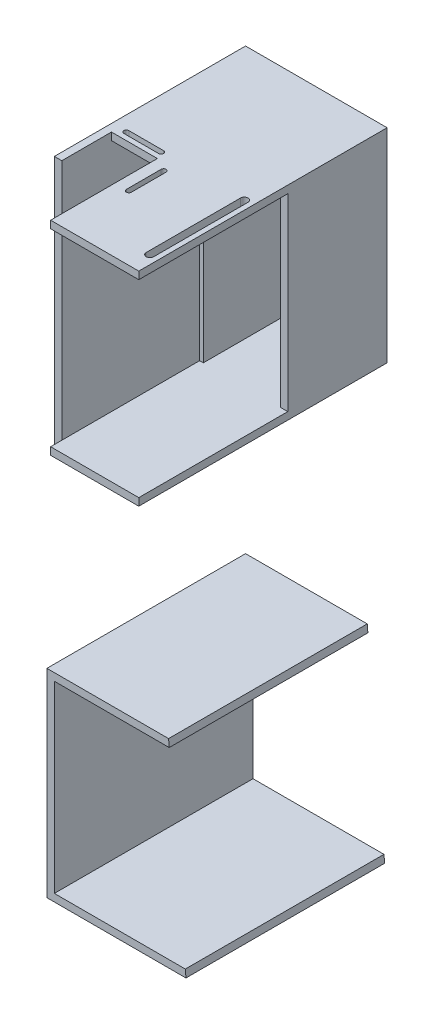
SolidWorks part; units mm, degrees
note: The reader was unsure of these and kept them because the rebuilt part matched: shared geometry of "스케치1<3>", "스케치1<5>", "스케치1<7>", "스케치7<3>", "스케치1<8>".
ref_plane "정면" through (0, 0, 0) normal (0, 0, 1) x (1, 0, 0)
ref_plane "윗면" through (0, 0, 0) normal (0, 1, 0) x (1, 0, 0)
ref_plane "우측면" through (0, 0, 0) normal (1, 0, 0) x (0, 0, -1)
sketch "스케치1" plane through (0, 0, 0) normal (0, 0, 1) x (1, 0, 0)
  line L0 (0, 0) -> (61, 0)
  line L2 (57, 82) -> (0, 82)
  line L3 (0, 82) -> (0, 0)
  line L4 (57.1463, 79) -> (3, 79)
  line L5 (3, 79) -> (3, 3)
  line L6 (3, 3) -> (60.8537, 3)
  line L9 (61, 0) -> (60.8537, 3)
  line L10 (57.1463, 79) -> (57, 82)
  line L11 (0, -95.0333) -> (49, -95.0333)
  line L12 (0, -95.0333) -> (0, -175.0333)
  line L13 (0, -175.0333) -> (56, -175.0333)
  line L15 (49.2625, -98.0333) -> (3, -98.0333)
  line L16 (3, -98.0333) -> (3, -172.0333)
  line L17 (3, -172.0333) -> (55.7375, -172.0333)
  line L18 (49.2625, -98.0333) -> (49, -95.0333)
  line L19 (55.7375, -172.0333) -> (56, -175.0333)
  line L20 (0, 140.1376) -> (0, -278.5402) construction
  line L21 (-165.7064, 0) -> (202.0952, 0) construction
  line L22 (0, 0) -> (0, -20)
  line L23 (0, -20) -> (24.5, -20)
  line L24 (24.5, -20) -> (24.5, 0)
  line L25 (24.5, 0) -> (0, 0)
  line L27 (3, -17) -> (21.5, -17)
  line L28 (3, -17) -> (3, 0)
  line L29 (3, 0) -> (21.5, 0)
  line L30 (21.5, -17) -> (21.5, 0)
  dimension "D1" = 82
  dimension "D2" = 61
  dimension "D3" = 57
  dimension "D4" = 3
  dimension "D5" = 3
  dimension "D6" = 3
  dimension "D7" = 80
  dimension "D8" = 49
  dimension "D9" = 56
  dimension "D10" = 23
  dimension "D11" = 3
  dimension "D12" = 3
  dimension "D13" = 3
  dimension "D14" = 24.5
  dimension "D15" = 3
  dimension "D16" = 3
  dimension "D17" = 3
extrude "보스-돌출1" add sketch "스케치1" along normal blind 100 contours L6 L9 L0 L3 L2 L10 L4 L5
extrude "보스-돌출2" add sketch "스케치1<3>" along normal blind 80 separate body contours L13 L19 L17 L16 L15 L18 L11 L12
sketch "스케치1<3>" plane through (0, 0, 0) normal (0, 0, 1) x (1, 0, 0) same geometry as "스케치1"
sketch "스케치4" plane through (0, 82, 0) normal (0, 1, 0) x (1, 0, 0)
  line L0 (0, -100) -> (23, -100)
  line L1 (57, -100) -> (0, -100) construction
  line L2 (23, -100) -> (23, -77)
  line L3 (23, -77) -> (0, -77)
  line L4 (0, -100) -> (0, 0) construction
  line L5 (0, -77) -> (0, -100)
  dimension "D1" = 23
  dimension "D2" = 23
extrude "컷-돌출5" cut sketch "스케치4" against normal blind 80 contours L2 L3 L5 L0
sketch "스케치5" plane through (0, 82, 0) normal (0, 1, 0) x (1, 0, 0)
  line L0 (57, -100) -> (61, -100)
  line L1 (61, -100) -> (61, 0)
  line L2 (61, -100) -> (61, 0) construction
  line L3 (61, 0) -> (57, 0)
  line L4 (57, -100) -> (57, 0) construction
  line L5 (57, 0) -> (57, -100)
  dimension "D1" = 100
extrude "보스-돌출4" add sketch "스케치1<5>" along normal up to vertex (77 mm away) contours L30 L27 L28 L0 L22 L23 L24 up to point (0, 2, 77)
sketch "스케치1<5>" plane through (0, 0, 0) normal (0, 0, 1) x (1, 0, 0) same geometry as "스케치1"
sketch "스케치7" plane through (0, -20, 0) normal (0, -1, 0) x (1, 0, 0)
  line L0 (21.5, 108.9709) -> (3, 108.9709)
  line L1 (3, 10) -> (21.5, 10)
  line L2 (3, 10) -> (3, 108.9709)
  line L4 (21.5, 10) -> (21.5, 108.9709)
  line L5 (57.1463, 0) -> (3, 0) construction
  line L9 (0, 100) -> (0, 77) construction
  dimension "D1" = 3
  dimension "D2" = 10
  dimension "D3" = 18.5
extrude "컷-돌출8" cut sketch "스케치7" against normal blind 50 contours L2 L0 L4 L1
extrude "컷-돌출9" cut sketch "스케치5" against normal blind 105
sketch "스케치8" plane through (0, 82, 0) normal (0, 1, 0) x (1, 0, 0)
  line L0 (-18.9554, -57) -> (80.2299, -57) construction
  line L1 (57, -100) -> (23, -100) construction
  line L2 (23, -77) -> (0, -77) construction
  line L3 (6, -54) -> (20, -54) construction
  line L4 (6, -53) -> (20, -53)
  line L5 (6, -55) -> (20, -55)
  line L6 (27, -74) -> (27, -60) construction
  line L7 (26, -74) -> (26, -60)
  line L8 (28, -74) -> (28, -60)
  line L9 (53.5, -92) -> (53.5, -54) construction
  line L10 (13, -61.8484) -> (13, -52.1516) construction
  line L11 (23, -100) -> (23, -77) construction
  line L12 (23, -77) -> (3, -77)
  line L13 (23, -77) -> (23, -57)
  line L14 (23, -57) -> (3, -57)
  line L15 (3, -77) -> (3, -57)
  line L16 (52, -92) -> (52, -54)
  line L17 (55, -92) -> (55, -54)
  line L18 (57, -100) -> (57, 0) construction
  arc A0 (6, -53) -> (6, -55) centre (6, -54) ccw
  arc A1 (20, -55) -> (20, -53) centre (20, -54) ccw
  arc A2 (26, -74) -> (28, -74) centre (27, -74) ccw
  arc A3 (28, -60) -> (26, -60) centre (27, -60) ccw
  arc A4 (52, -92) -> (55, -92) centre (53.5, -92) ccw
  arc A5 (55, -54) -> (52, -54) centre (53.5, -54) ccw
  point P8 (13, -54)
  point P15 (27, -67)
  point P22 (13, -57)
  point P31 (53.5, -73)
  point P39 (13, -57)
  dimension "D2" = 1
  dimension "D3" = 1
  dimension "D10" = 1.5
  dimension "D1" = 20
  dimension "D4" = 10
  dimension "D6" = 3
  dimension "D7" = 3
  dimension "D8" = 14
  dimension "D9" = 14
  dimension "D11" = 38
  dimension "D12" = 8
  dimension "D13" = 2
extrude "컷-돌출11" cut sketch "스케치8" against normal blind 14 contours L14 L15 L12 L13 | L4 A1 L5 A0 | L8 A3 L7 A2 | L17 A5 L16 A4
sketch "스케치12" plane through (0, 82, 0) normal (0, 1, 0) x (1, 0, 0)
  line L1 (57, 0) -> (54, 0)
  line L2 (57, 0) -> (57, -40)
  line L3 (57, -40) -> (54, -40)
  line L4 (54, 0) -> (54, -40)
  dimension "D1" = 3
  dimension "D2" = 40
extrude "보스-돌출8" add sketch "스케치12" against normal up to vertex (79 mm away) contours L4 L3 L2 L1
sketch "스케치14" plane through (0, 3, 0) normal (0, 1, 0) x (1, 0, 0)
  line L0 (3, 0) -> (60.8537, 0) construction
  line L1 (21.5, -77) -> (23, -77)
  line L2 (21.5, -77) -> (21.5, 0)
  line L3 (21.5, 0) -> (23, 0)
  line L4 (23, -77) -> (23, 0)
  line L7 (21.5, -77) -> (21.5, -10) construction
  line L9 (23, -100) -> (23, -77) construction
extrude "보스-돌출11" add sketch "스케치14" along normal up to vertex (79 mm away) up to point (26, 82, 74)
sketch "스케치15" plane through (57, 0, 0) normal (1, 0, 0) x (0, 0, -1)
  line L1 (-77, 79) -> (-40, 79)
  line L2 (-77, 79) -> (-77, 3)
  line L3 (-77, 3) -> (-40, 3)
  line L4 (-40, 79) -> (-40, 3)
extrude "컷-돌출12" cut sketch "스케치15" against normal blind 46
sketch "스케치16" plane through (0, 3, 0) normal (0, 1, 0) x (1, 0, 0)
  line L0 (23, -100) -> (57, -100) construction
  line L1 (0, -77) -> (21.5, -77)
  line L2 (0, -77) -> (0, -100)
  line L3 (0, -100) -> (21.5, -100)
  line L4 (21.5, -77) -> (21.5, -100)
  line L6 (21.5, -40) -> (21.5, -77) construction
  line L7 (3, -77) -> (0, -77) construction
extrude "컷-돌출13" cut sketch "스케치16" against normal blind 10
extrude "보스-돌출12" add sketch "스케치1<7>" along normal up to vertex (77 mm away) contours L22 L23 L24 L25 up to point (24.5, 0, 77)
sketch "스케치1<7>" plane through (0, 0, 0) normal (0, 0, 1) x (1, 0, 0) same geometry as "스케치1"
extrude "컷-돌출14" cut sketch "스케치7<3>" against normal up to vertex (20 mm away) contours L2 L0 L4 L1 up to point (21.5, 0, 0)
sketch "스케치7<3>" plane through (0, -20, 0) normal (0, -1, 0) x (1, 0, 0) same geometry as "스케치7"
extrude "컷-돌출15" cut sketch "스케치1<8>" along normal blind 17 contours L27 L30 L29 L28
sketch "스케치1<8>" plane through (0, 0, 0) normal (0, 0, 1) x (1, 0, 0) same geometry as "스케치1"
sketch "스케치19" plane through (0, 82, 0) normal (0, 1, 0) x (1, 0, 0)
  line L1 (21.5, -77) -> (23, -77)
  line L2 (21.5, -77) -> (21.5, -100)
  line L3 (21.5, -100) -> (23, -100)
  line L4 (23, -77) -> (23, -100)
extrude "보스-돌출13" add sketch "스케치19" against normal up to vertex
sketch "스케치20" plane through (0, 0, 100) normal (0, 0, 1) x (1, 0, 0)
  line L0 (23, 3) -> (57, 3) construction
  line L1 (23, 2) -> (21.5, 2)
  line L2 (23, 2) -> (23, 3)
  line L3 (23, 3) -> (21.5, 3)
  line L4 (21.5, 2) -> (21.5, 3)
  line L5 (21.5, 0) -> (21.5, 2) construction
extrude "보스-돌출14" add sketch "스케치20" against normal up to vertex (100 mm away) contours L3 L4 L1 L2
